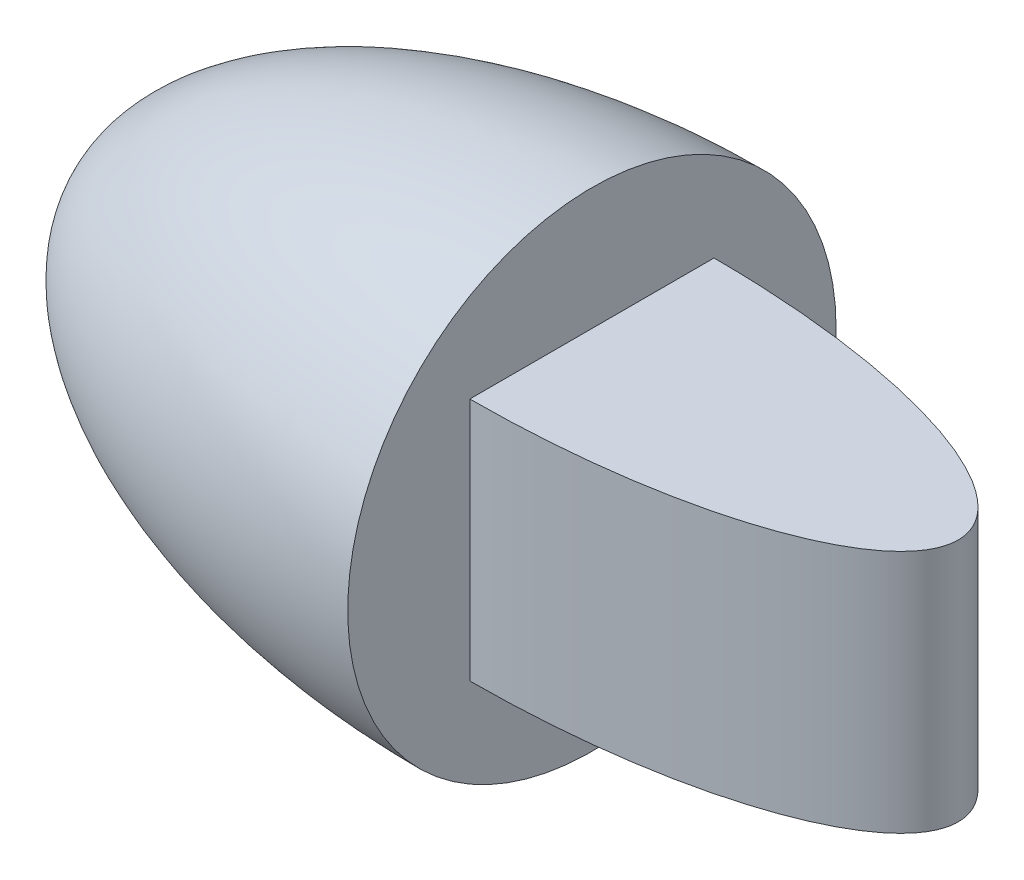
SolidWorks part; units mm, degrees
ref_plane "Alzado" through (0, 0, 0) normal (0, 0, 1) x (1, 0, 0)
ref_plane "Planta" through (0, 0, 0) normal (0, 1, 0) x (1, 0, 0)
ref_plane "Vista lateral" through (0, 0, 0) normal (1, 0, 0) x (0, 0, -1)
sketch "Sketch1" plane through (0, 0, 0) normal (0, 1, 0) x (1, 0, 0)
  line L0 (-75, 0) -> (75, 0) construction
  ellipse E0 centre (0, 0) end of major axis (75, 0) minor radius 25
  dimension "D1" = 50
  dimension "D2" = 150
extrude "Boss-Extrude1" add sketch "Sketch1" along normal blind 25 and the other way blind 25
sketch "Sketch2" plane through (0, 25, 0) normal (0, 1, 0) x (1, 0, 0)
  line L0 (0, 0) -> (75, 0) construction
  ellipse E0 centre (0, 0) end of major axis (75, 0) minor radius 25 construction
  point P9 (50, 0)
  dimension "D1" = 25
ref_axis "Axis1" through (50, 25, 0) along (0, 1, 0)
sketch "Sketch3" plane through (0, 0, 0) normal (0, 1, 0) x (1, 0, 0)
  line L0 (0, 0) -> (-100, 0)
  line L1 (0, 0) -> (0, 50)
  ellipse E0 centre (0, 0) end of major axis (-100, 0) minor radius 50 (-100, 0) -> (0, 50) cw
  dimension "D1" = 100
  dimension "D2" = 50
revolve "Revolve1" add sketch "Sketch3" angle 360 about L0
